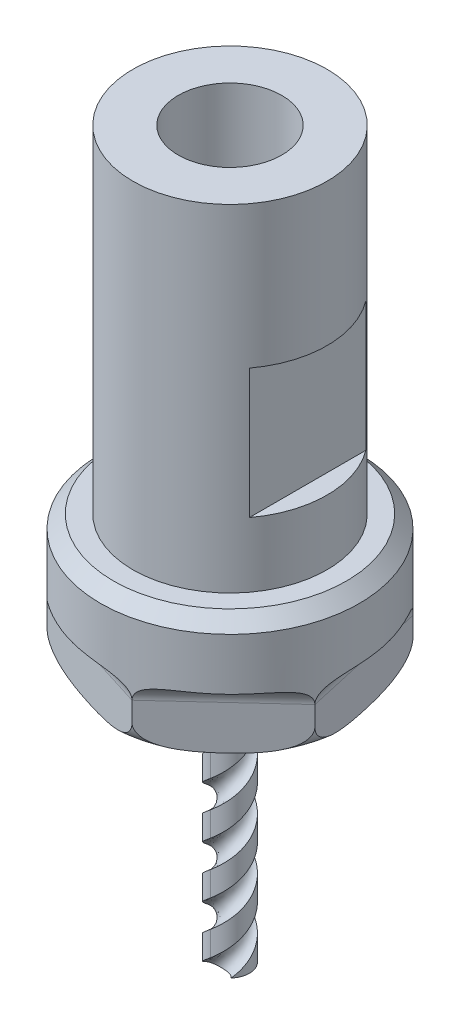
SolidWorks part; units mm, degrees
material "普通碳钢"
ref_plane "前视基准面" through (0, 0, 0) normal (0, 0, 1) x (1, 0, 0)
ref_plane "上视基准面" through (0, 0, 0) normal (0, 1, 0) x (1, 0, 0)
ref_plane "右视基准面" through (0, 0, 0) normal (1, 0, 0) x (0, 0, -1)
sketch "草图1" plane through (0, 0, 0) normal (0, 1, 0) x (1, 0, 0)
  circle A0 centre (0, 0) radius 7.5
  circle A1 centre (0, 0) radius 4
  dimension "D1" = 15
  dimension "D2" = 8
extrude "凸台-拉伸1" add sketch "草图1" along normal blind 26
ref_plane "基准面1" through (0, 5, 0) normal (0, 1, 0) x (1, 0, 0)
sketch "草图4" plane through (0, 5, 0) normal (0, 1, 0) x (1, 0, 0)
  line L0 (-6, 4.5) -> (-6, -4.5)
  line L1 (0, 7.5) -> (0, -7.5) construction
  line L2 (6, 4.5) -> (6, -4.5)
  circle A0 centre (0, 0) radius 7.5 construction
  arc A1 (-6, 4.5) -> (-6, -4.5) centre (0, 0) ccw
  arc A2 (6, -4.5) -> (6, 4.5) centre (0, 0) ccw
  dimension "D1" = 6
extrude "切除-拉伸1" cut sketch "草图4" along normal blind 10
sketch "草图9" plane through (0, 0, 0) normal (0, 0, 1) x (1, 0, 0)
  line L0 (0, 31.3849) -> (0, -23.2502) construction
  line L1 (0, 0) -> (9, 0)
  line L2 (10, -1) -> (10, -8)
  line L3 (8, -10) -> (0, -10)
  line L4 (9, 0) -> (10, -1)
  line L5 (0, 0) -> (0, -10)
  arc A0 (10, -8) -> (8, -10) centre (8, -8) cw
  point P4 (10, 0)
  dimension "D3" = 2
  dimension "D1" = 10
  dimension "D2" = 10
revolve "旋转1" add sketch "草图9" angle 360 about L0
sketch "草图10" plane through (0, -10, 0) normal (0, -1, 0) x (1, 0, 0)
  line L1 (7.3576, -6.7725) -> (9.5439, 2.9856)
  line L2 (9.5439, 2.9856) -> (2.1863, 9.7581)
  line L3 (2.1863, 9.7581) -> (-7.3576, 6.7725)
  line L4 (-7.3576, 6.7725) -> (-9.5439, -2.9856)
  line L5 (-9.5439, -2.9856) -> (-2.1863, -9.7581)
  line L6 (-2.1863, -9.7581) -> (7.3576, -6.7725)
  circle A0 centre (0, 0) radius 10 construction
  circle A1 centre (0, 0) radius 10
  circle A2 centre (0, 0) radius 8.6603 construction
extrude "切除-拉伸4" cut sketch "草图10" against normal blind 5 contours L1 A1 | L2 A1 | L3 A1 | L4 A1 | L5 A1 | L6 A1 region at (2.7466, -10, -8.7798) region at (8.9768, -10, -2.0113) region at (6.2302, -10, 6.7685) region at (-6.2302, -10, -6.7685) region at (-2.7466, -10, 8.7798) region at (-8.9768, -10, 2.0113)
fillet "圆角17" radius 1.5 3 edges at (2.5856, -5, -8.2653) (5.8651, -5, 6.3718) (-8.4507, -5, 1.8934)
fillet "圆角18" radius 1.5 3 edges at (-5.8651, -5, -6.3718) (8.4507, -5, -1.8934) (-2.5856, -5, 8.2653)
sketch "草图11" plane through (0, -10, 0) normal (0, -1, 0) x (1, 0, 0)
  circle A0 centre (0, 0) radius 1.5
extrude "凸台-拉伸4" add sketch "草图11" along normal blind 20
sketch "草图12" plane through (0, -30, 0) normal (0, -1, 0) x (1, 0, 0)
  circle A0 centre (0, 0) radius 1.5 construction
  circle A1 centre (0, 0) radius 1.5
curve "螺旋线/涡状线1" pitch 8 height 16 radius 1.5 centre (0, -30, 0) axis (0, 1, 0) start towards (0, 0, -1)
sketch "草图13" plane through (0, -30, 0) normal (0, -1, 0) x (1, 0, 0)
  circle A0 centre (0, 0) radius 1.5 construction
  circle A1 centre (0, 0) radius 1.5
ref_plane "基准面4" through (0, -30, -1.5) normal (-0.7624, 0.6471, 0) x (0, 0, 1)
sketch "草图15" plane through (0, -30, -1.5) normal (-0.7624, 0.6471, 0) x (0, 0, 1)
  line L1 (0, 0) -> (-0.5657, -0.5657)
  line L2 (0, 0) -> (-0.5657, 0.5657)
  arc A0 (-0.5657, -0.5657) -> (-0.5657, 0.5657) centre (0, 0) ccw
  dimension "D1" = 0.8
sweep "切除-扫描3" cut profiles "草图15" path "螺旋线/涡状线1" align with end faces yes
ref_axis "基准轴1" through (0, 28.8655, 0) along (0, -1, 0)
pattern_circular "阵列(圆周)1" count 2 every 180 about axis through (0, 28.8655, 0) along (0, -1, 0) of "切除-扫描3"
